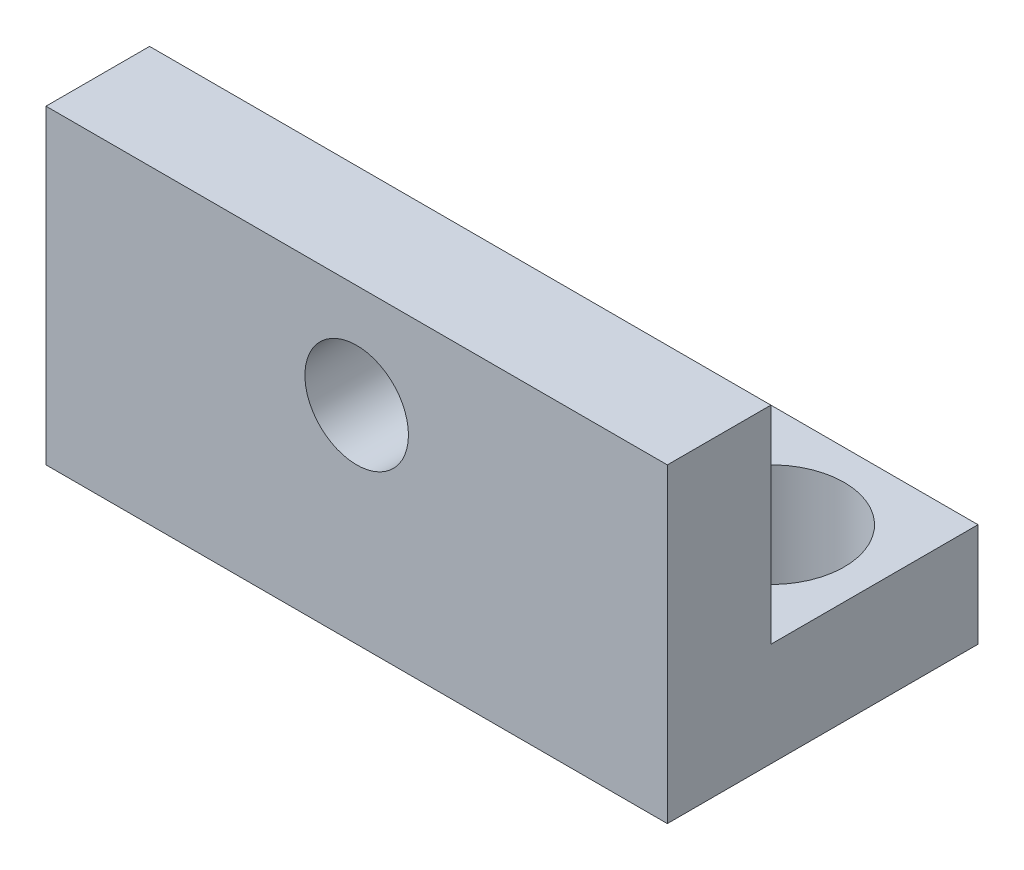
SolidWorks part; units mm, degrees
material "ABS"
ref_plane "Front Plane" through (0, 0, 0) normal (0, 0, 1) x (1, 0, 0)
ref_plane "Top Plane" through (0, 0, 0) normal (0, 1, 0) x (1, 0, 0)
ref_plane "Right Plane" through (0, 0, 0) normal (1, 0, 0) x (0, 0, -1)
sketch "Sketch1" plane through (0, 0, 0) normal (0, 0, 1) x (1, 0, 0)
  line L1 (-9.525, -3.175) -> (9.525, -3.175)
  line L2 (-9.525, -3.175) -> (-9.525, 3.175)
  line L3 (-9.525, 3.175) -> (9.525, 3.175)
  line L4 (9.525, -3.175) -> (9.525, 3.175)
  line L5 (-9.525, -3.175) -> (9.525, 3.175) construction
  line L6 (-9.525, 3.175) -> (9.525, -3.175) construction
  circle A0 centre (0, 0) radius 1.5875
  point P0 (0, 0)
  dimension "D3" = 3.175
  dimension "D1" = 6.35
  dimension "D2" = 19.05
extrude "Boss-Extrude1" add sketch "Sketch1" along normal blind 3.175
sketch "Sketch2" plane through (0, -3.175, 0) normal (0, -1, 0) x (1, 0, 0)
  line L0 (-9.525, 3.175) -> (9.525, 3.175) construction
  line L1 (-9.525, 3.175) -> (9.525, 3.175)
  line L2 (-9.525, 3.175) -> (-9.525, -6.35)
  line L3 (-9.525, -6.35) -> (9.525, -6.35)
  line L4 (9.525, 3.175) -> (9.525, -6.35)
  line L5 (-9.525, 3.175) -> (-9.525, 0) construction
  line L7 (3.4925, 0) -> (-3.4925, 0) construction
  point P8 (9.525, 3.175)
  dimension "D1" = 6.35
extrude "Boss-Extrude2" add sketch "Sketch2" along normal blind 3.175
hole_wizard "#8 Clearance Hole1" positions "Sketch3" profile "Sketch4" hole size "#8" standard "ANSI Inch" end condition through all
sketch "Sketch3" plane through (0, -6.35, 0) normal (0, -1, 0) x (-1, 0, 0)
  line L0 (9.525, 3.175) -> (-9.525, 3.175) construction
  line L1 (9.525, 0) -> (9.525, 6.35) construction
  line L2 (-9.525, 6.35) -> (-9.525, 0) construction
  line L4 (0, 6.35) -> (0, -3.175) construction
  line L5 (9.525, 6.35) -> (-9.525, 6.35) construction
  line L6 (-9.525, -3.175) -> (9.525, -3.175) construction
  line L8 (-9.525, 6.35) -> (-9.525, -3.175) construction
  point P9 (6.35, 3.175)
  point P11 (-6.35, 3.175)
  dimension "D1" = 3.175
sketch "Sketch4" plane through (6.35, -6.35, -3.175) normal (1, 0, 0) x (0, 0, -1)
  line L0 (0, 0) -> (0, 9.525)
  line L1 (0, 9.525) -> (2.2479, 9.525)
  line L2 (2.2479, 9.525) -> (2.2479, 0)
  line L5 (2.2479, 0) -> (0, 0)
  line L11 (0, -6.35) -> (0, 107.95) construction
  dimension "Thru Hole Dia." = 4.4958
  dimension "Thru Hole Depth" = 9.525
